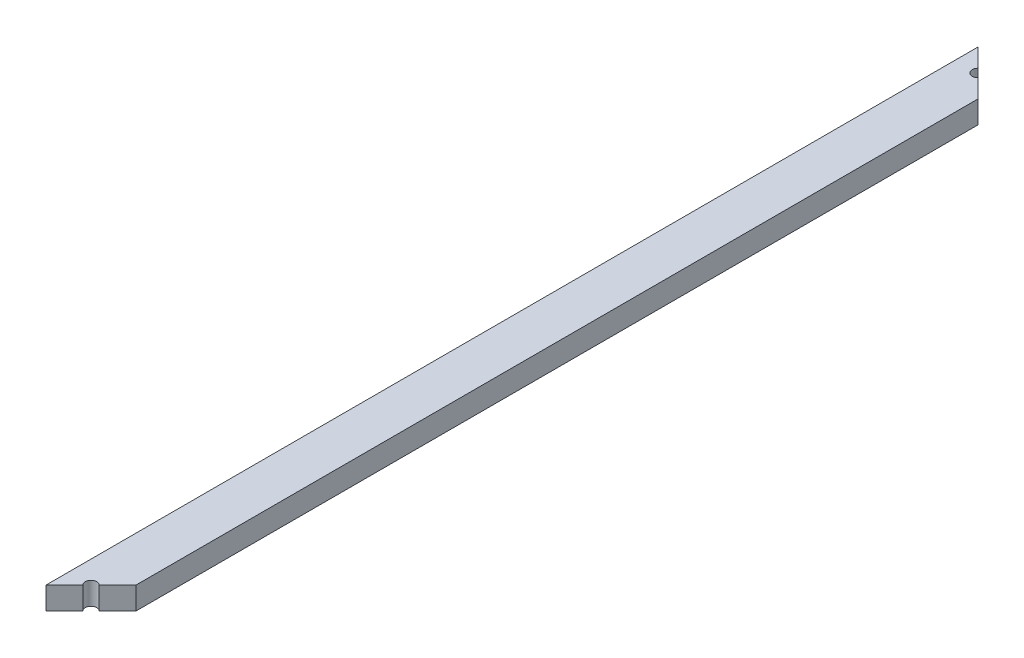
SolidWorks part; units mm, degrees
ref_plane "Front Plane" through (0, 0, 0) normal (0, 0, 1) x (1, 0, 0)
ref_plane "Top Plane" through (0, 0, 0) normal (0, 1, 0) x (1, 0, 0)
ref_plane "Right Plane" through (0, 0, 0) normal (1, 0, 0) x (0, 0, -1)
sketch "Sketch1" plane through (0, 0, 0) normal (0, 0, 1) x (1, 0, 0)
  line L1 (0, 0) -> (14, 0)
  line L2 (0, 0) -> (0, 7)
  line L3 (0, 7) -> (14, 7)
  line L4 (14, 0) -> (14, 7)
  dimension "D1" = 7
  dimension "D2" = 14
extrude "Boss-Extrude1" add sketch "Sketch1" along normal blind 290
sketch "Sketch2" plane through (0, 7, 0) normal (0, 1, 0) x (1, 0, 0)
  line L0 (0, 0) -> (14, -14)
  line L1 (14, -290) -> (14, 0) construction
  line L2 (14, -14) -> (14, 0)
  line L3 (14, 0) -> (0, 0)
  line L4 (14, -145) -> (0, -145) construction
  line L5 (0, -290) -> (0, 0) construction
  line L6 (14, -290) -> (0, -290)
  line L7 (14, -276) -> (14, -290)
  line L8 (0, -290) -> (14, -276)
  dimension "D1" = 45
extrude "Cut-Extrude1" cut sketch "Sketch2" against normal through all
sketch "Sketch3" plane through (0, 7, 0) normal (0, 1, 0) x (1, 0, 0)
  line L0 (0, 0) -> (14, -14) construction
  line L1 (0, -145) -> (14, -145) construction
  line L2 (0, -290) -> (0, 0) construction
  line L3 (14, -276) -> (14, -14) construction
  line L4 (5.7272, -5.7272) -> (8.2728, -8.2728)
  line L5 (5.7272, -284.2728) -> (8.2728, -281.7272)
  arc A0 (5.7272, -5.7272) -> (8.2728, -8.2728) centre (7, -7) ccw
  arc A1 (5.7272, -284.2728) -> (8.2728, -281.7272) centre (7, -283) cw
  dimension "D1" = 3.6
extrude "Cut-Extrude2" cut sketch "Sketch3" against normal through all
